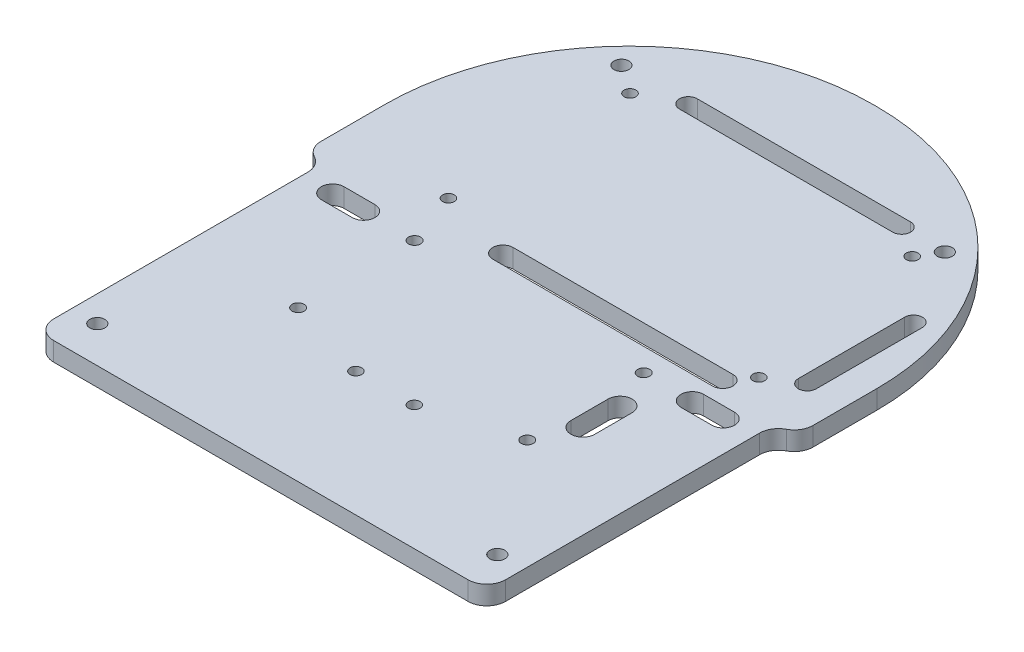
SolidWorks part; units mm, degrees
ref_plane "Front Plane" through (0, 0, 0) normal (0, 0, 1) x (1, 0, 0)
ref_plane "Top Plane" through (0, 0, 0) normal (0, 1, 0) x (1, 0, 0)
ref_plane "Right Plane" through (0, 0, 0) normal (1, 0, 0) x (0, 0, -1)
sketch "Sketch1" plane through (0, 0, 0) normal (0, 1, 0) x (1, 0, 0)
  line L0 (0, 90.99) -> (0, -94.01) construction
  line L1 (-94.5795, 0) -> (90.4205, 0) construction
  line L2 (-65.5, 80) -> (-65.5, -83.5)
  line L3 (-65.5, -83.5) -> (65.5, -83.5)
  line L4 (65.5, -83.5) -> (65.5, 80)
  line L5 (65.5, 80) -> (-65.5, 80)
  line L6 (-65.5, -7) -> (-65.5, -83.5)
  line L7 (-65.5, -83.5) -> (-60.15, -83.5)
  line L8 (-60.15, -83.5) -> (-60.15, -7)
  line L9 (-60.15, -7) -> (-65.5, -7)
  line L10 (60.15, -83.5) -> (60.15, -7)
  line L11 (65.5, -83.5) -> (60.15, -83.5)
  line L12 (65.5, -7) -> (65.5, -83.5)
  line L13 (60.15, -7) -> (65.5, -7)
  dimension "D1" = 60.15
  dimension "D2" = 65.5
  dimension "D3" = 80
  dimension "D4" = 185
  dimension "D5" = 185
  dimension "D7" = 76.5
  dimension "D8" = 87
  dimension "D9" = 65.5
extrude "Boss-Extrude2" add sketch "Sketch1" along normal blind 5 contours L10 L13 L4 L5 L2 L9 L8 L7 L3 L11 region at (0, 0, 0.0215)
fillet "Fillet8" radius 65 2 edges at (65.5, 2.5, -80) (-65.5, 2.5, -80)
sketch "Sketch4" plane through (0, 5, 0) normal (0, 1, 0) x (1, 0, 0)
  line L0 (0, 0) -> (0, 80) construction
  line L1 (0, 80) -> (0, -83.5) construction
  line L2 (35.3092, -23.1757) -> (35.3092, -33.0901) construction
  line L3 (-65.5, 4) -> (65.5, 4) construction
  line L4 (-65.5, 15) -> (-65.5, -7) construction
  line L5 (65.5, -7) -> (65.5, 15) construction
  line L6 (-60.15, -83.5) -> (-60.15, -7) construction
  line L7 (0.5, 80) -> (-0.5, 80) construction
  line L8 (-60.15, -83.5) -> (60.15, -83.5) construction
  line L9 (60.15, -83.5) -> (60.15, -7) construction
  line L10 (-60.15, -45.25) -> (60.15, -45.25) construction
  line L27 (38.4857, -23.1757) -> (38.4857, -33.0901)
  line L28 (32.1327, -23.1757) -> (32.1327, -33.0901)
  line L29 (-25.2292, 55.5443) -> (31.548, 55.5443) construction
  line L32 (-60.15, -83.5) -> (-60.15, -7) construction
  line L33 (-60.15, -83.5) -> (60.15, -83.5) construction
  line L34 (-25.2292, 57.9144) -> (31.548, 57.9144)
  line L35 (-25.2292, 53.1741) -> (31.548, 53.1741)
  line L36 (-15.4719, -3.5901) -> (43.0471, -3.5901) construction
  line L37 (-15.4719, -0.8869) -> (43.0471, -0.8869)
  line L38 (-15.4719, -6.2934) -> (43.0471, -6.2934)
  line L39 (55.1066, 35.1494) -> (55.1066, 6.8682) construction
  line L40 (57.4842, 35.1494) -> (57.4842, 6.8682)
  line L41 (52.729, 35.1494) -> (52.729, 6.8682)
  line L42 (-60.15, -83.5) -> (60.15, -83.5) construction
  line L43 (60.15, -83.5) -> (60.15, -7) construction
  line L44 (-65.5, 15) -> (-65.5, -7) construction
  line L45 (-51.9956, -12.3973) -> (-43.7542, -12.3973) construction
  line L46 (-51.9956, -9.3872) -> (-43.7542, -9.3872)
  line L47 (-51.9956, -15.4074) -> (-43.7542, -15.4074)
  line L48 (51.9956, -12.3973) -> (43.7542, -12.3973) construction
  line L49 (51.9956, -9.3872) -> (43.7542, -9.3872)
  line L50 (51.9956, -15.4074) -> (43.7542, -15.4074)
  circle A38 centre (43.0471, 55.5443) radius 2
  circle A41 centre (-43.0471, 55.5443) radius 2
  circle A51 centre (-53.249, -73.7963) radius 2
  circle A52 centre (53.249, -73.7963) radius 2
  circle A53 centre (-35.419, 50.1936) radius 1.5621
  circle A54 centre (39.7142, 50.1936) radius 1.5621
  circle A55 centre (-35.419, 1.8574) radius 1.5621
  circle A56 centre (47.2072, 1.8574) radius 1.5621
  circle A57 centre (-30.1836, -12.3973) radius 1.6
  circle A58 centre (30.8164, -12.3973) radius 1.6
  circle A59 centre (30.8164, -43.3973) radius 1.6
  circle A60 centre (-30.1836, -43.3973) radius 1.6
  arc A61 (38.4857, -23.1757) -> (32.1327, -23.1757) centre (35.3092, -23.1757) ccw
  arc A62 (32.1327, -33.0901) -> (38.4857, -33.0901) centre (35.3092, -33.0901) ccw
  arc A63 (-25.2292, 57.9144) -> (-25.2292, 53.1741) centre (-25.2292, 55.5443) ccw
  arc A64 (31.548, 53.1741) -> (31.548, 57.9144) centre (31.548, 55.5443) ccw
  arc A65 (-15.4719, -0.8869) -> (-15.4719, -6.2934) centre (-15.4719, -3.5901) ccw
  arc A66 (43.0471, -6.2934) -> (43.0471, -0.8869) centre (43.0471, -3.5901) ccw
  arc A67 (57.4842, 35.1494) -> (52.729, 35.1494) centre (55.1066, 35.1494) ccw
  arc A68 (52.729, 6.8682) -> (57.4842, 6.8682) centre (55.1066, 6.8682) ccw
  circle A69 centre (-7.869, -50.3336) radius 1.5558
  circle A70 centre (7.6885, -50.3336) radius 1.5558
  arc A71 (-51.9956, -9.3872) -> (-51.9956, -15.4074) centre (-51.9956, -12.3973) ccw
  arc A72 (-43.7542, -15.4074) -> (-43.7542, -9.3872) centre (-43.7542, -12.3973) ccw
  arc A73 (51.9956, -9.3872) -> (51.9956, -15.4074) centre (51.9956, -12.3973) cw
  arc A74 (43.7542, -15.4074) -> (43.7542, -9.3872) centre (43.7542, -12.3973) cw
  point P30 (35.3092, -28.1329)
  point P39 (3.1594, 55.5443)
  point P50 (55.1066, 21.0088)
  point P54 (13.7876, -3.5901)
  point P70 (-47.8749, -12.3973)
  point P87 (47.8749, -12.3973)
  point P93 (-51.9956, -12.3973)
  dimension "D2" = 3.1242
  dimension "D13" = 4
  dimension "D10" = 3.2
  dimension "D11" = 3.2
  dimension "D5" = 3.1242
  dimension "D6" = 2.7033
  dimension "D7" = 58.519
  dimension "D18" = 39.7142
  dimension "D8" = 3.2
  dimension "D22" = 15.4719
  dimension "D23" = 55.1066
  dimension "D3" = 3.1242
  dimension "D4" = 3.1242
  dimension "D9" = 3.2
  dimension "D12" = 3.1765
  dimension "D20" = 47.2072
  dimension "D21" = 4
  dimension "D24" = 2.3776
  dimension "D26" = 79.9099
  dimension "D25" = 28.2812
  dimension "D37" = 2.3702
  dimension "D38" = 28.602
  dimension "D45" = 3.1115
  dimension "D46" = 3.1115
  dimension "D51" = 3.0101
  dimension "D14" = 6.901
  dimension "D15" = 9.7037
  dimension "D16" = 9.9145
  dimension "D17" = 35.419
  dimension "D19" = 35.419
  dimension "D27" = 85.3574
  dimension "D28" = 85.3574
  dimension "D29" = 30.1836
  dimension "D30" = 30.1836
  dimension "D31" = 30.8164
  dimension "D32" = 30.8164
  dimension "D33" = 71.1027
  dimension "D34" = 71.1027
  dimension "D35" = 40.1027
  dimension "D36" = 40.1027
  dimension "D39" = 40.2708
  dimension "D40" = 90.3682
  dimension "D41" = 35.3092
  dimension "D42" = 50.4099
  dimension "D43" = 133.6936
  dimension "D44" = 133.6936
  dimension "D47" = 7.869
  dimension "D48" = 7.6885
  dimension "D49" = 33.1664
  dimension "D50" = 33.1664
  dimension "D52" = 43.7542
  dimension "D53" = 8.2414
  dimension "D54" = 71.1027
extrude "Cut-Extrude1" cut sketch "Sketch4" against normal blind 5
ref_plane "Plane1" through (60.15, 5, 7) normal (0, 0, -1) x (-1, 0, 0)
fillet "Fillet9" radius 5 4 edges at (65.5, 2.5, 7) (60.15, 2.5, 83.5) (-60.15, 2.5, 83.5) (-65.5, 2.5, 7)
fillet "Fillet10" radius 5 2 edges at (60.15, 2.5, 7) (-60.15, 2.5, 7)
